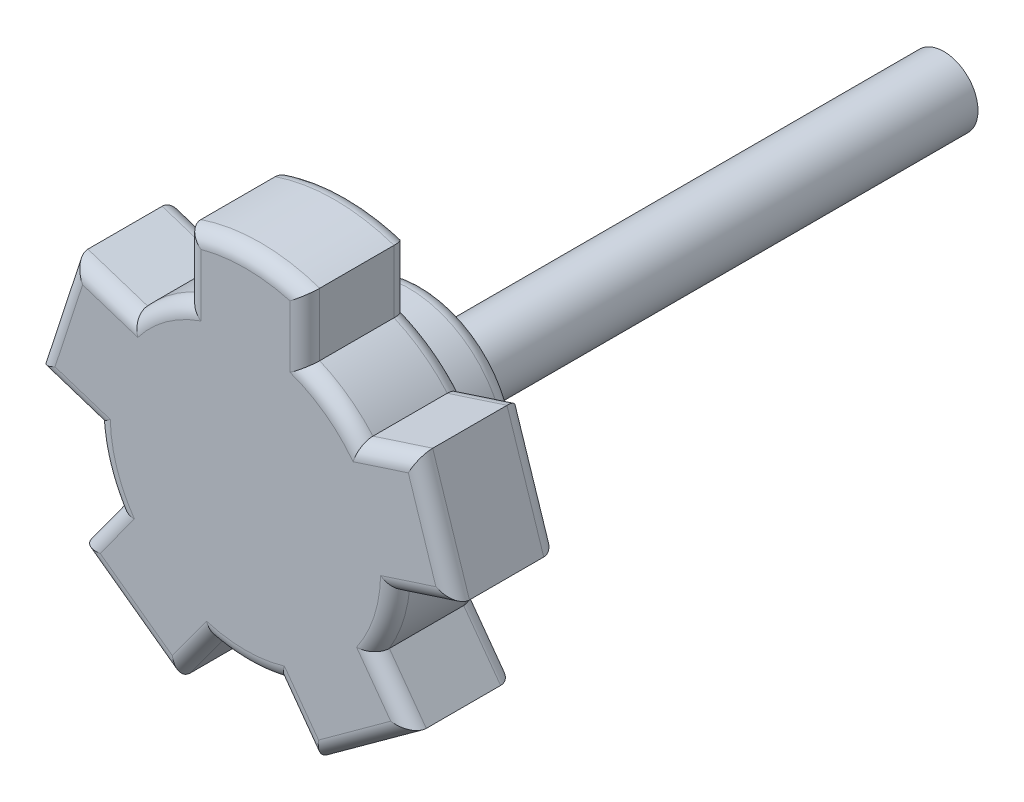
SolidWorks part; units mm, degrees
ref_plane "Front Plane" through (0, 0, 0) normal (0, 0, 1) x (1, 0, 0)
ref_plane "Top Plane" through (0, 0, 0) normal (0, 1, 0) x (1, 0, 0)
ref_plane "Right Plane" through (0, 0, 0) normal (1, 0, 0) x (0, 0, -1)
sketch "Sketch1" plane through (0, 0, 0) normal (0, 0, 1) x (1, 0, 0)
  circle A0 centre (0, 0) radius 2.921
extrude "Extrude1" add sketch "Sketch1" along normal blind 44.45
sketch "Sketch2" plane through (0, 0, 44.45) normal (0, 0, 1) x (1, 0, 0)
  circle A0 centre (0, 0) radius 8.255
extrude "Extrude2" add sketch "Sketch2" along normal blind 6.35
sketch "Sketch3" plane through (0, 0, 50.8) normal (0, 0, 1) x (1, 0, 0)
  circle A0 centre (0, 0) radius 12.827
extrude "Extrude3" add sketch "Sketch3" along normal blind 8.89
sketch "Sketch4" plane through (0, 0, 59.69) normal (0, 0, 1) x (1, 0, 0)
  line L0 (5.08, 11.7782) -> (5.08, 17.145) construction
  line L1 (-5.08, 11.7782) -> (-5.08, 17.145) construction
  line L2 (9.6319, 8.471) -> (14.7361, 10.1295)
  line L3 (14.7361, 10.1295) -> (17.8757, 0.4667)
  line L4 (0, 12.827) -> (0, 11.557) construction
  line L5 (-5.08, 11.7782) -> (-5.08, 17.145)
  line L6 (12.7715, -1.1917) -> (17.8757, 0.4667)
  line L7 (12.7715, -1.1917) -> (17.8757, 0.4667) construction
  line L8 (-5.08, 17.145) -> (5.08, 17.145)
  line L9 (5.08, 11.7782) -> (5.08, 17.145)
  line L10 (9.6319, 8.471) -> (14.7361, 10.1295) construction
  line L11 (12.1992, 3.9638) -> (10.9914, 3.5713) construction
  line L12 (11.0328, -6.5428) -> (14.1874, -10.8846)
  line L13 (14.1874, -10.8846) -> (5.9678, -16.8565)
  line L14 (2.8132, -12.5147) -> (5.9678, -16.8565)
  line L15 (2.8132, -12.5147) -> (5.9678, -16.8565) construction
  line L16 (11.0328, -6.5428) -> (14.1874, -10.8846) construction
  line L17 (7.5395, -10.3773) -> (6.793, -9.3498) construction
  line L18 (-2.8132, -12.5147) -> (-5.9678, -16.8565)
  line L19 (-5.9678, -16.8565) -> (-14.1874, -10.8846)
  line L20 (-11.0328, -6.5428) -> (-14.1874, -10.8846)
  line L21 (-11.0328, -6.5428) -> (-14.1874, -10.8846) construction
  line L22 (-2.8132, -12.5147) -> (-5.9678, -16.8565) construction
  line L23 (-7.5395, -10.3773) -> (-6.793, -9.3498) construction
  line L24 (-12.7715, -1.1917) -> (-17.8757, 0.4667)
  line L25 (-17.8757, 0.4667) -> (-14.7361, 10.1295)
  line L26 (-9.6319, 8.471) -> (-14.7361, 10.1295)
  line L27 (-9.6319, 8.471) -> (-14.7361, 10.1295) construction
  line L28 (-12.7715, -1.1917) -> (-17.8757, 0.4667) construction
  line L29 (-12.1992, 3.9638) -> (-10.9914, 3.5713) construction
  circle A0 centre (0, 0) radius 12.827 construction
  arc A1 (-5.08, 11.7782) -> (5.08, 11.7782) centre (0, 0) cw
  arc A2 (9.6319, 8.471) -> (12.7715, -1.1917) centre (0, 0) cw
  arc A3 (11.0328, -6.5428) -> (2.8132, -12.5147) centre (0, 0) cw
  arc A4 (-2.8132, -12.5147) -> (-11.0328, -6.5428) centre (0, 0) cw
  arc A5 (-12.7715, -1.1917) -> (-9.6319, 8.471) centre (0, 0) cw
sketch "Sketch6" plane through (0, 0, 0) normal (0, 1, 0) x (1, 0, 0)
  line L0 (0, -62.9081) -> (0, 0) construction
extrude "Extrude6" add sketch "Sketch4" against normal up to surface (8.89 mm away) up to face at (12.827, 0, 50.8)
sketch "Sketch7" plane through (0, 0, 59.69) normal (0, 0, 1) x (1, 0, 0)
  line L0 (5.08, 17.145) -> (-5.08, 17.145)
  arc A0 (-5.08, 17.145) -> (5.08, 17.145) centre (0, 2.2854) cw
extrude "Extrude7" add sketch "Sketch7" against normal up to surface (8.89 mm away) up to face at (0, 0, 50.8)
fillet "Fillet1" radius 1.27 42 edges at (7.5395, 10.3773, 50.8) (5.08, 14.4616, 50.8) (0, 17.9894, 50.8) (-5.08, 14.4616, 50.8) (-7.5395, 10.3773, 50.8) (8.255, 0, 50.8) (-5.08, 14.4616, 59.69) (0, 17.9894, 59.69) (5.08, 14.4616, 59.69) (7.5395, 10.3773, 59.69) (-7.5395, 10.3773, 59.69) (8.255, 0, 44.45) (-12.184, 9.3002, 50.8) (-16.3059, 5.2981, 50.8) (-15.3236, -0.3625, 50.8) (-12.1992, -3.9638, 50.8) (-12.6101, -8.7137, 50.8) (-10.0776, -13.8706, 50.8) (-4.3905, -14.6856, 50.8) (0, -12.827, 50.8) (4.3905, -14.6856, 50.8) (10.0776, -13.8706, 50.8) (12.6101, -8.7137, 50.8) (12.1992, -3.9638, 50.8) (15.3236, -0.3625, 50.8) (16.3059, 5.2981, 50.8) (12.184, 9.3002, 50.8) (12.184, 9.3002, 59.69) (16.3059, 5.2981, 59.69) (15.3236, -0.3625, 59.69) (12.1992, -3.9638, 59.69) (12.6101, -8.7137, 59.69) (10.0776, -13.8706, 59.69) (4.3905, -14.6856, 59.69) (0, -12.827, 59.69) (-4.3905, -14.6856, 59.69) (-10.0776, -13.8706, 59.69) (-12.6101, -8.7137, 59.69) (-12.1992, -3.9638, 59.69) (-15.3236, -0.3625, 59.69) (-16.3059, 5.2981, 59.69) (-12.184, 9.3002, 59.69)
